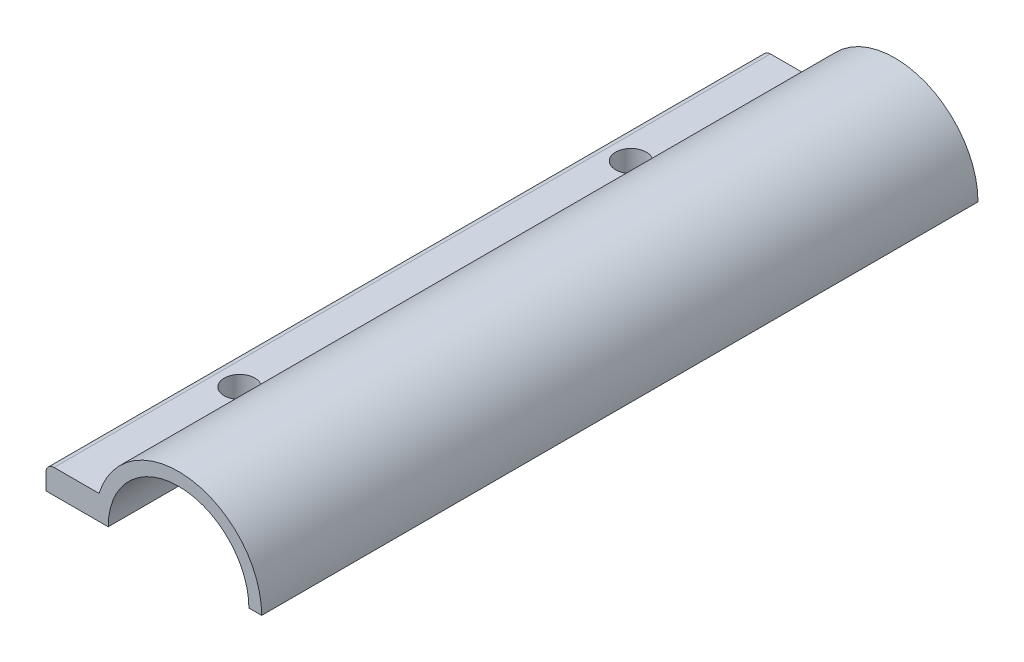
SolidWorks part; units mm, degrees
material "ABS"
ref_plane "X-Y Datum" through (0, 0, 0) normal (0, 0, 1) x (1, 0, 0)
ref_plane "X-Z Datum" through (0, 0, 0) normal (0, 1, 0) x (1, 0, 0)
ref_plane "Y-Z Datum" through (0, 0, 0) normal (1, 0, 0) x (0, 0, -1)
sketch "Sketch1" plane through (0, 0, 0) normal (0, 0, 1) x (1, 0, 0)
  line L0 (-13, 0) -> (-20.7245, 0)
  line L1 (-20.7245, 0) -> (-20.7245, -13)
  line L2 (-20.7245, -13) -> (0, -13)
  line L3 (-13, 0) -> (13, 0)
  line L4 (0, 13) -> (-20.7245, 13)
  line L5 (-20.7245, 13) -> (-20.7245, 0)
  line L6 (-20.7245, 3.81) -> (-12.4292, 3.81)
  circle A0 centre (0, 0) radius 13
  circle A1 centre (0, 0) radius 11
  dimension "D3" = 2
  dimension "D2" = 22
  dimension "D1" = 7.7245
  dimension "D4" = 3.81
extrude "Boss-Extrude1" add sketch "Sketch1" along normal blind 112 contours A1 L3 A0 | A0 L6 L5 L0 region at (-12.569, 1.8832, 0) region at (-16.7661, 1.9278, 0)
sketch "Sketch3" plane through (0, 3.81, 0) normal (0, 1, 0) x (1, 0, 0)
  circle A0 centre (-15.8622, -25.4) radius 3.025 construction
  circle A1 centre (-15.8622, -86.6) radius 3.025 construction
  circle A2 centre (-15.8622, -25.4) radius 3.025 construction
  circle A3 centre (-15.8622, -86.6) radius 3.025 construction
  point P0 (-15.8622, -25.4)
  point P2 (-15.8622, -86.6)
fillet "Fillet1" radius 1.27 1 edges at (-20.7245, 3.81, 56)
hole_wizard "M4 Clearance Hole1" positions "Sketch3" profile "Sketch5" hole size "M4" standard "ANSI Metric" end condition through all
sketch "Sketch5" plane through (-15.8622, 3.81, 25.4) normal (1, 0, 0) x (0, 0, 1)
  line L0 (0, 0) -> (0, 3.81)
  line L1 (0, 3.81) -> (2.4, 3.81)
  line L2 (2.4, 3.81) -> (2.4, 0)
  line L5 (2.4, 0) -> (0, 0)
  line L11 (0, -6.35) -> (0, 107.95) construction
  dimension "Thru Hole Dia." = 4.8
  dimension "Thru Hole Depth" = 3.81
